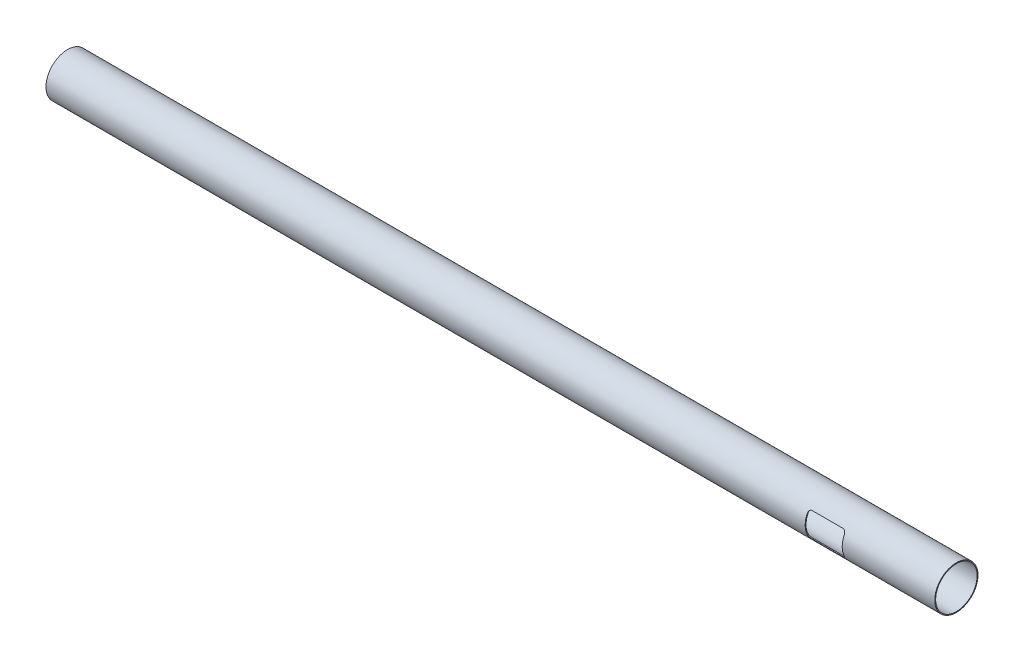
SolidWorks part; units mm, degrees
ref_plane "Front" through (0, 0, 0) normal (0, 0, 1) x (1, 0, 0)
ref_plane "Top" through (0, 0, 0) normal (0, 1, 0) x (1, 0, 0)
ref_plane "Right" through (0, 0, 0) normal (1, 0, 0) x (0, 0, -1)
sketch "Sketch1" plane through (0, 0, 0) normal (1, 0, 0) x (0, 0, -1)
  line L0 (21.336, 0) -> (22.225, 0) construction
  line L1 (21.336, 0) -> (22.225, 0) construction
  line L2 (21.7805, 0) -> (21.7805, 1.0672) construction
  circle A0 centre (0, 0) radius 22.225
  circle A1 centre (0, 0) radius 21.336
  point P4 (22.225, 0)
  point P5 (21.336, 0)
  dimension "OD" = 44.45
  dimension "ID" = 42.672
  dimension "Wall Thickness" = 0.889
sketch "Sketch2" plane through (0, 0, 0) normal (0, 0, 1) x (1, 0, 0)
  line L0 (-457.2, 0) -> (457.2, 0) construction
  point P2 (-401.6375, 0)
  point P3 (401.6375, 0)
  dimension "D1" = 55.5625
  dimension "D2" = 55.5625
sketch "Sketch3" plane through (0, 0, 0) normal (1, 0, 0) x (0, 0, -1)
  circle A0 centre (0, 0) radius 21.336 construction
  circle A1 centre (0, 0) radius 22.225 construction
  circle A2 centre (0, 0) radius 21.336
  circle A3 centre (0, 0) radius 22.225
extrude "Boss-Extrude1" add sketch "Sketch3" along normal mid plane 914.4
sketch "Sketch4" plane through (0, 0, 0) normal (0, 0, 1) x (1, 0, 0)
  line L0 (457.2, 0) -> (228.6, 0) construction
  line L1 (358.775, 12.7) -> (327.025, 12.7)
  line L2 (361.95, 9.525) -> (361.95, -9.525)
  line L3 (358.775, -12.7) -> (327.025, -12.7)
  line L4 (323.85, 9.525) -> (323.85, -9.525)
  line L5 (361.95, 12.7) -> (323.85, -12.7) construction
  line L6 (361.95, -12.7) -> (323.85, 12.7) construction
  line L7 (457.2, -22.225) -> (457.2, 22.225) construction
  arc A0 (361.95, -9.525) -> (358.775, -12.7) centre (358.775, -9.525) cw
  arc A1 (358.775, 12.7) -> (361.95, 9.525) centre (358.775, 9.525) cw
  arc A2 (327.025, 12.7) -> (323.85, 9.525) centre (327.025, 9.525) ccw
  arc A3 (327.025, -12.7) -> (323.85, -9.525) centre (327.025, -9.525) cw
  point P0 (342.9, 0)
  dimension "D3" = 3.175
  dimension "D1" = 38.1
  dimension "D2" = 25.4
  dimension "D4" = 228.6
extrude "Cut-Extrude1" cut sketch "Sketch4" along normal through all
equation "\"D1@Boss-Extrude1\"=\"Length@Sketch2\""
equation "\"D1@Sketch2\"=\"OD@Sketch1\"*1.25"
equation "\"D2@Sketch2\"=\"D1@Sketch2\""
